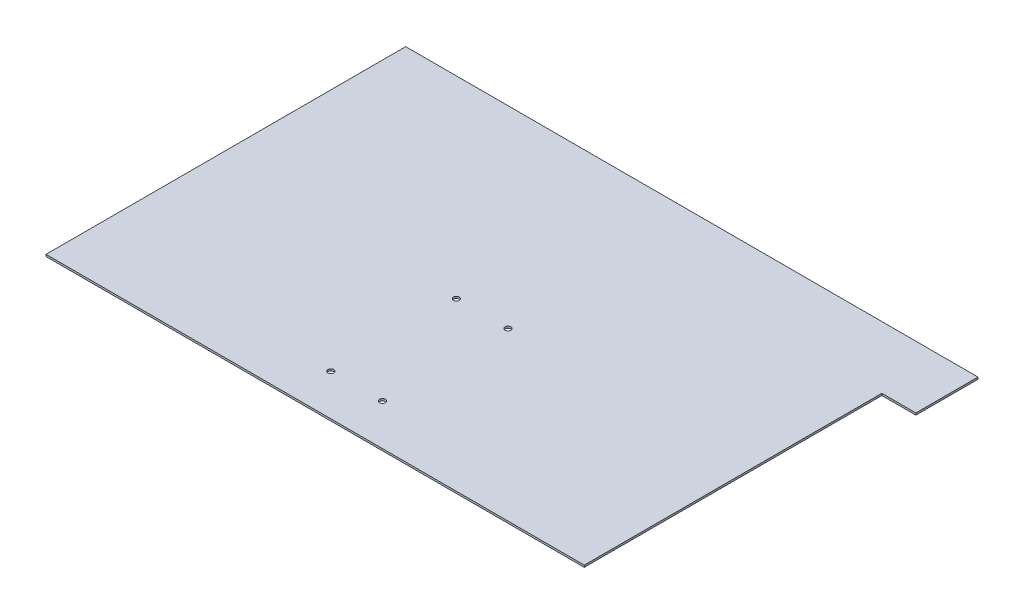
SolidWorks part; units mm, degrees
ref_plane "Front Plane" through (0, 0, 0) normal (0, 0, 1) x (1, 0, 0)
ref_plane "Top Plane" through (0, 0, 0) normal (0, 1, 0) x (1, 0, 0)
ref_plane "Right Plane" through (0, 0, 0) normal (1, 0, 0) x (0, 0, -1)
sketch "Sketch1" plane through (0, 0, 0) normal (0, 1, 0) x (1, 0, 0)
  line L0 (411.5, 275) -> (463.5, 275)
  line L1 (-411.5, 275) -> (411.5, 275)
  line L2 (-411.5, 275) -> (-411.5, -275)
  line L3 (-411.5, -275) -> (411.5, -275)
  line L4 (411.5, 180) -> (411.5, -275)
  line L5 (-411.5, 275) -> (411.5, -275) construction
  line L6 (-411.5, -275) -> (411.5, 275) construction
  line L7 (81.6416, -116) -> (-39, -116) construction
  line L8 (463.5, 275) -> (463.5, 180)
  line L9 (463.5, 180) -> (411.5, 180)
  circle A14 centre (-39, -212) radius 4.5
  circle A15 centre (-39, -20) radius 4.5
  circle A16 centre (40, -20) radius 4.5
  circle A17 centre (40, -212) radius 4.5
  point P0 (0, 0)
  dimension "D5" = 79
  dimension "D7" = 9
  dimension "D1" = 550
  dimension "D2" = 823
  dimension "D3" = 96
  dimension "D4" = 372.5
  dimension "D8" = 95
  dimension "D9" = 255
  dimension "D6" = 52
base flange "Base-Flange1" sketch "Sketch1" thickness 3 reverse thickness direction no parameters "D1"=0.7366
sketch "Bend-Lines1" [suppressed] plane through (0, 0, 0) normal (0, 1, 0) x (1, 0, 0)
sketch "Bounding-Box1" [suppressed] plane through (0, 0, 0) normal (0, 1, 0) x (1, 0, 0)
sheet metal parameters "Sheet-Metal1" thickness 3 parameters "D1"=0.7366
flat pattern "Flat-Pattern1" [suppressed]
sketch "Bend-Lines2" plane through (0, 0, 0) normal (0, 1, 0) x (1, 0, 0)
sketch3d "Bounding-Box2" [suppressed]
  line L0 (463.5, -275, 0) -> (-411.5, -275, 0) construction
  line L1 (463.5, 275, 0) -> (-411.5, 275, 0) construction
  line L2 (463.5, -275, 0) -> (463.5, 275, 0) construction
  line L3 (-411.5, -275, 0) -> (-411.5, 275, 0) construction
